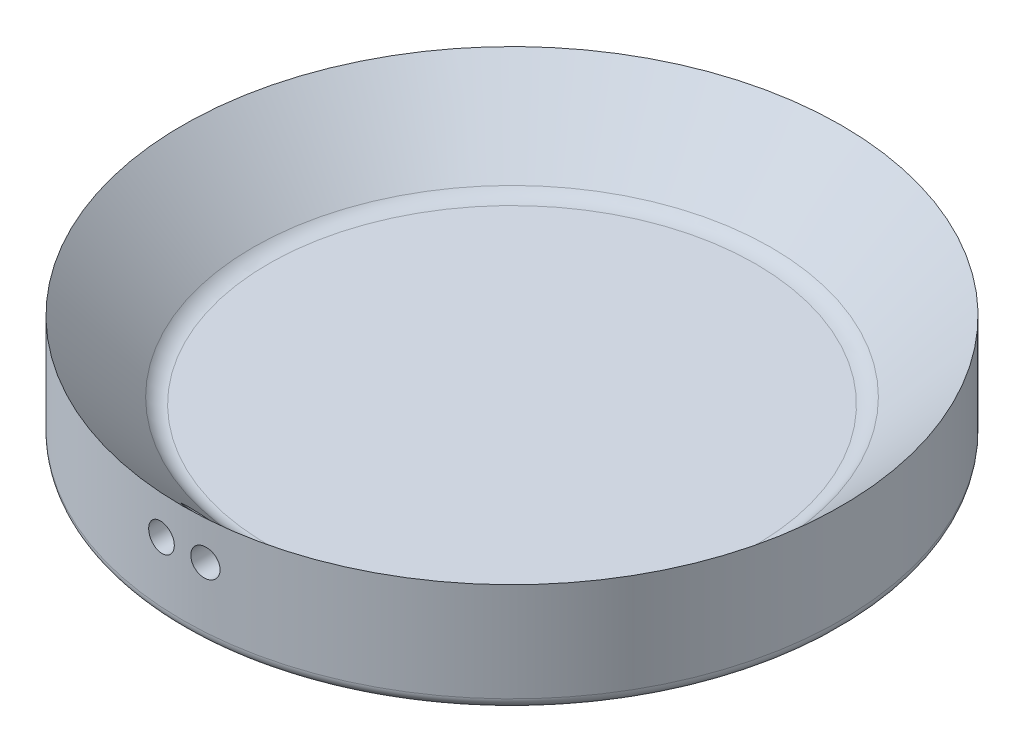
SolidWorks part; units mm, degrees
ref_plane "Front Plane" through (0, 0, 0) normal (0, 0, 1) x (1, 0, 0)
ref_plane "Top Plane" through (0, 0, 0) normal (0, 1, 0) x (1, 0, 0)
ref_plane "Right Plane" through (0, 0, 0) normal (1, 0, 0) x (0, 0, -1)
sketch "Sketch3" plane through (0, 0, 0) normal (0, 0, 1) x (1, 0, 0)
  line L4 (-23, 0) -> (0, 0)
  line L9 (-22.1716, 3) -> (0, 3)
  line L10 (0, 0) -> (0, 3)
  line L12 (-23, 3) -> (-23, 10) construction
  line L13 (-23, 10) -> (-30, 10) construction
  line L15 (-30, 10) -> (-23.5858, 3.5858)
  line L16 (-23, 0) -> (-29, 0)
  line L17 (-30, 1) -> (-30, 10)
  arc A4 (-30, 1) -> (-29, 0) centre (-29, 1) ccw
  arc A5 (-23.5858, 3.5858) -> (-22.1716, 3) centre (-22.1716, 5) ccw
  dimension "D1" = 7
  dimension "D6" = 1
  dimension "D7" = 2
  dimension "D2" = 23
  dimension "D3" = 23
  dimension "D4" = 3
  dimension "D5" = 7
revolve "Revolve3" add sketch "Sketch3" angle 360 about L10
ref_plane "Plane1" through (0, 0, 30) normal (0, 0, 1) x (1, 0, 0)
sketch "Sketch5" plane through (0, 0, 30) normal (0, 0, 1) x (1, 0, 0)
  line L0 (0, 10) -> (0, 3) construction
  line L2 (30, 10) -> (-30, 10) construction
  line L3 (-2, 6.5) -> (2, 6.5) construction
  circle A0 centre (-2, 6.5) radius 1.25
  circle A1 centre (2, 6.5) radius 1.25
  point P8 (0, 6.5)
  point P9 (0, 6.5)
  dimension "D3" = 2.5
  dimension "D4" = 2.5
  dimension "D1" = 7
  dimension "D2" = 4
extrude "Cut-Extrude1" cut sketch "Sketch5" against normal up to next
